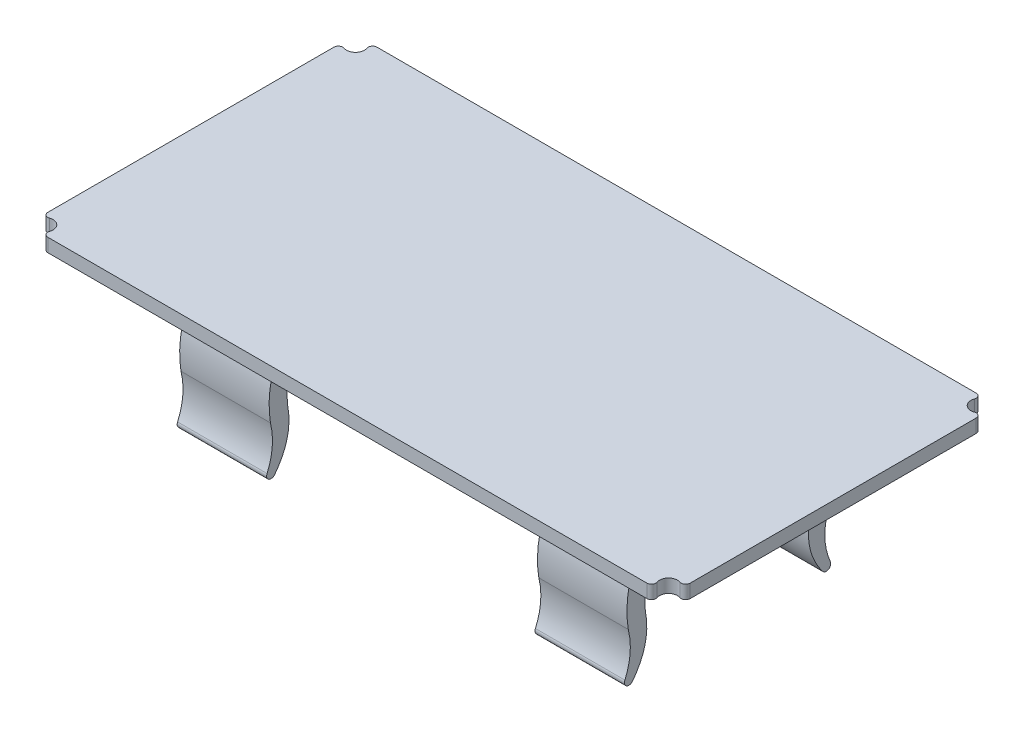
SolidWorks part; units mm, degrees
note: The reader was unsure of these and kept them because the rebuilt part matched: shared geometry of "Sketch3<3>".
ref_plane "Front Plane" through (0, 0, 0) normal (0, 0, 1) x (1, 0, 0)
ref_plane "Top Plane" through (0, 0, 0) normal (0, 1, 0) x (1, 0, 0)
ref_plane "Right Plane" through (0, 0, 0) normal (1, 0, 0) x (0, 0, -1)
sketch "Sketch1" plane through (0, 0, 0) normal (0, 1, 0) x (1, 0, 0)
  line L1 (2.4142, 0) -> (69.3858, 0)
  line L2 (0, 2.4142) -> (0, 34.3858)
  line L3 (2.4142, 36.8) -> (69.3858, 36.8)
  line L4 (71.8, 2.4142) -> (71.8, 34.3858)
  arc A0 (0.6667, 34.8572) -> (1.9428, 36.1333) centre (1, 35.8) ccw
  arc A1 (1.9428, 0.6667) -> (0.6667, 1.9428) centre (1, 1) ccw
  arc A2 (71.1333, 1.9428) -> (69.8572, 0.6667) centre (70.8, 1) ccw
  arc A3 (69.8572, 36.1333) -> (71.1333, 34.8572) centre (70.8, 35.8) ccw
  arc A4 (69.8572, 36.1333) -> (69.3858, 36.8) centre (69.3858, 36.3) ccw
  arc A5 (71.8, 34.3858) -> (71.1333, 34.8572) centre (71.3, 34.3858) ccw
  arc A6 (71.1333, 1.9428) -> (71.8, 2.4142) centre (71.3, 2.4142) ccw
  arc A7 (69.8572, 0.6667) -> (69.3858, 0) centre (69.3858, 0.5) cw
  arc A8 (2.4142, 0) -> (1.9428, 0.6667) centre (2.4142, 0.5) cw
  arc A9 (0, 2.4142) -> (0.6667, 1.9428) centre (0.5, 2.4142) ccw
  arc A10 (2.4142, 36.8) -> (1.9428, 36.1333) centre (2.4142, 36.3) ccw
  arc A11 (0, 34.3858) -> (0.6667, 34.8572) centre (0.5, 34.3858) cw
  dimension "D3" = 1
  dimension "D7" = 1
  dimension "D2" = 0.5
  dimension "D4" = 1
  dimension "D5" = 1
  dimension "D6" = 1
  dimension "D8" = 1
  dimension "D9" = 1
  dimension "D10" = 1
extrude "Boss-Extrude1" add sketch "Sketch1" along normal blind 1.5
sketch "Sketch2" plane through (0, 0, 0) normal (0, -1, 0) x (1, 0, 0)
  line L0 (0, -18.4) -> (71.8, -18.4) construction
  line L1 (0, -34.3858) -> (0, -2.4142) construction
  line L2 (71.8, -2.4142) -> (71.8, -34.3858) construction
  line L3 (3, -12.6466) -> (68, -12.6466) construction
  dimension "D1" = 65
  dimension "D2" = 3
sketch "Sketch3" plane through (0, 0, 0) normal (-1, 0, 0) x (0, 0, 1)
  line L0 (-36.8, 1.5) -> (-36.8, 0) construction
  line L1 (-24.426, 0) -> (-12.374, 0)
  line L2 (-18.4, 0) -> (-18.4, -19) construction
  line L3 (-34.3858, 0) -> (-2.4142, 0) construction
  line L4 (-29.0322, -16.5661) -> (-7.7678, -16.5661) construction
  arc A0 (-24.426, 0) -> (-29.5008, -11.3264) centre (-18.4, -9.5) ccw
  arc A1 (-9.2006, -10.4666) -> (-27.5994, -10.4666) centre (-18.4, -9.5) ccw
  arc A2 (-29.8798, -16.0437) -> (-29.0322, -16.5661) centre (-29.4315, -16.2652) ccw
  circle A3 centre (-18.4, -9.5) radius 11.25 construction
  arc A5 (-6.9202, -16.0437) -> (-7.7678, -16.5661) centre (-7.3685, -16.2652) cw
  arc A8 (-7.2992, -11.3264) -> (-12.374, 0) centre (-18.4, -9.5) ccw
  circle A10 centre (-18.4, -9.5) radius 9.25 construction
  spline S0 degree 2 poles (-29.5008, -11.3264) (-28.8973, -13.7518) (-29.8798, -16.0437) knots 0 0 0 1 1 1
  spline S1 degree 2 poles (-27.5994, -10.4666) (-26.9077, -13.8178) (-29.0322, -16.5661) knots 0 0 0 1 1 1
  spline S2 degree 2 poles (-7.2992, -11.3264) (-7.9027, -13.7518) (-6.9202, -16.0437) knots 0 0 0 1 1 1
  spline S3 degree 2 poles (-9.2006, -10.4666) (-9.8923, -13.8178) (-7.7678, -16.5661) knots 0 0 0 1 1 1
  point P2 (-36.8, 0.75)
  point P5 (-18.4, -9.5)
  point P6 (-33.8544, -1.1798)
  point P7 (-32.928, 0)
  point P12 (-25.4426, -5.8774)
  point P13 (-7.4, -9.5)
  point P15 (-7.4, -9.5)
  point P20 (-26.369, -7.0572)
  point P23 (-9.3151, -6.7225)
  point P29 (-9.3151, -6.7225)
  dimension "D1" = 18.4
  dimension "D4" = 0.5
  dimension "D5" = 6.026
  dimension "D6" = 18.5
  dimension "D7" = 6.026
  dimension "D2" = 9.5
  dimension "D3" = 2
extrude "Boss-Extrude2" add sketch "Sketch3" against normal blind 10 from offset 10 offset against normal yes
extrude "Boss-Extrude3" add sketch "Sketch3<3>" against normal blind 10 from offset 50 offset against normal yes
sketch "Sketch3<3>" plane through (0, 0, 0) normal (-1, 0, 0) x (0, 0, 1) same geometry as "Sketch3"
fillet "Fillet1" radius 2 4 edges at (55, 0, -24.426) (15, 0, -24.426) (55, 0, -12.374) (15, 0, -12.374)
